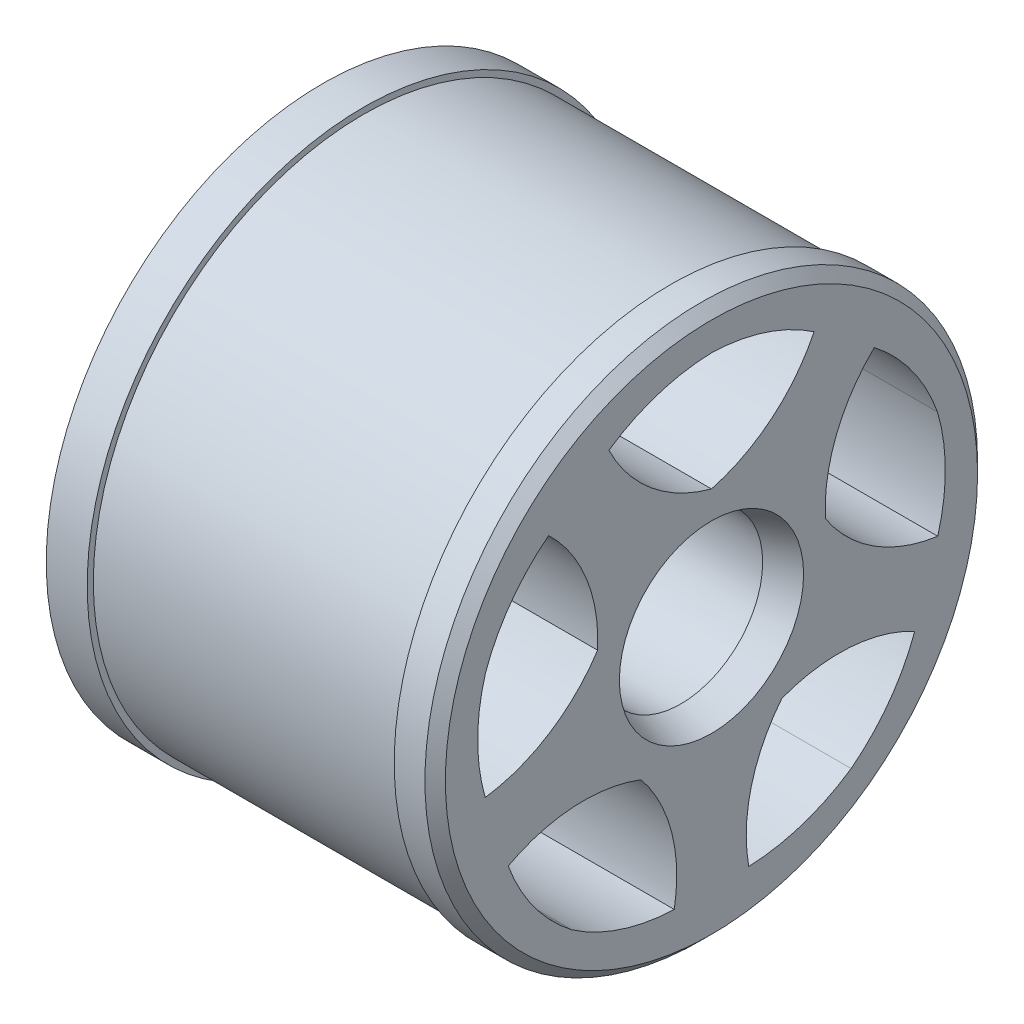
SolidWorks part; units mm, degrees
ref_plane "Front Plane" through (0, 0, 0) normal (0, 0, 1) x (1, 0, 0)
ref_plane "Top Plane" through (0, 0, 0) normal (0, 1, 0) x (1, 0, 0)
ref_plane "Right Plane" through (0, 0, 0) normal (1, 0, 0) x (0, 0, -1)
sketch "Sketch1" plane through (0, 0, 0) normal (1, 0, 0) x (0, 0, -1)
  circle A0 centre (0, 0) radius 13.5
  circle A1 centre (0, 0) radius 4
  dimension "D1" = 27
  dimension "D2" = 8
extrude "Boss-Extrude1" add sketch "Sketch1" along normal mid plane 19
sketch "Sketch2" plane through (0, 0, 0) normal (1, 0, 0) x (0, 0, -1)
  line L0 (0, 0) -> (0, 14.8201) construction
  arc A0 (0, 5.8497) -> (-5.0122, 9.994) centre (2.0377, 13.4173) cw
  arc A1 (-5.0122, 9.994) -> (0, 11.6087) centre (0.2591, 2.218) cw
  arc A2 (5.0122, 9.994) -> (0, 11.6087) centre (-0.2591, 2.218) ccw
  arc A3 (0, 5.8497) -> (5.0122, 9.994) centre (-2.0377, 13.4173) ccw
extrude "Cut-Extrude1" cut sketch "Sketch2" along normal through all both and the other way through all
pattern_circular "CirPattern1" count 5 over 360 about axis through (9.5, 0, 0) along (-1, 0, 0) of "Cut-Extrude1" reverse direction yes
chamfer "Chamfer1" distance 0.5 angle 45 1 edges at (9.5, 0, -13.5)
sketch "Sketch4" plane through (0, 0, 0) normal (1, 0, 0) x (0, 0, -1)
  circle A0 centre (0, 0) radius 13.5
  circle A1 centre (0, 0) radius 13.2
  circle A2 centre (0, 0) radius 13.5 construction
  dimension "D1" = 0.3
extrude "Cut-Extrude3" cut sketch "Sketch4" against normal mid plane 15
chamfer "Chamfer2" distance 0.5 distance2 1.5 1 edges at (9.5, 0, -4) first distance on face at (9.5, 0, -13)
equation "\"axis_diameter\"=5.66"
equation "\"padding\"=0.5"
